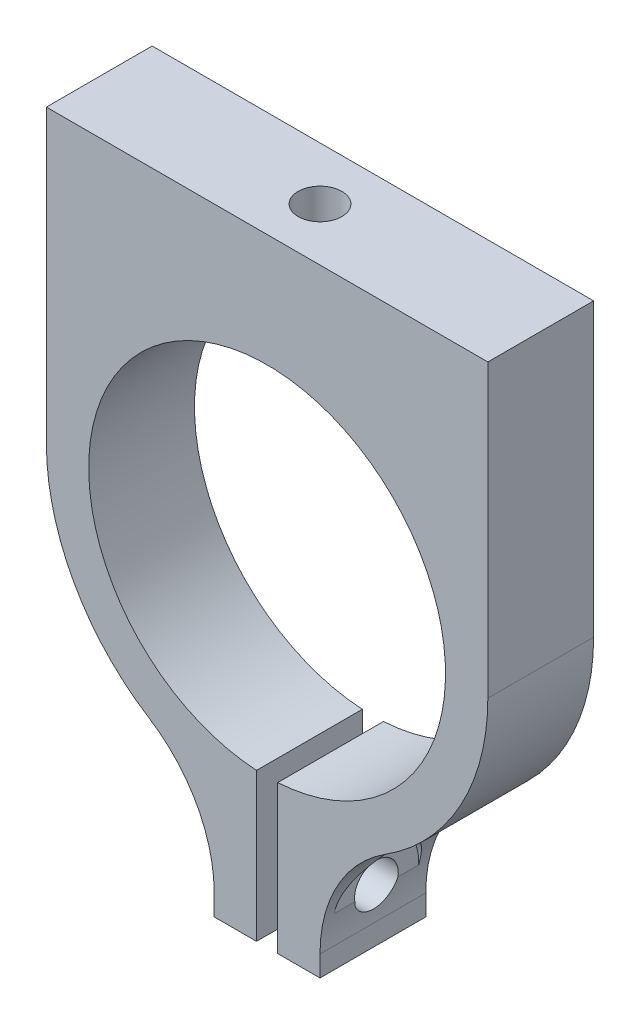
SolidWorks part; units mm, degrees
material "PLA"
ref_plane "Front Plane" through (0, 0, 0) normal (0, 0, 1) x (1, 0, 0)
ref_plane "Top Plane" through (0, 0, 0) normal (0, 1, 0) x (1, 0, 0)
ref_plane "Right Plane" through (0, 0, 0) normal (1, 0, 0) x (0, 0, -1)
sketch "Sketch1" plane through (0, 0, 0) normal (0, 0, 1) x (1, 0, 0)
  line L0 (-15.65, 0) -> (-15.65, 15.65)
  line L1 (-15.65, 15.65) -> (15.65, 15.65)
  line L2 (15.65, 15.65) -> (15.65, 0)
  line L4 (-0.75, -18.6277) -> (0.75, -18.6277)
  line L5 (-0.75, -18.6277) -> (-0.75, -12.6277)
  line L6 (-0.75, -12.6277) -> (0.75, -12.6277)
  line L7 (0.75, -18.6277) -> (0.75, -12.6277)
  line L8 (0, -44.7868) -> (0, 44.7868) construction
  circle A0 centre (0, 0) radius 12.65
  circle A1 centre (0, 0) radius 15.65
  dimension "D1" = 25.3
  dimension "D2" = 31.3
  dimension "D3" = 1.5
  dimension "D4" = 0.75
  dimension "D5" = 6
extrude "Boss-Extrude1" add sketch "Sketch1" along normal mid plane 40 contours A1 L1 L0 | A1 L2 L1 | A1 L5 A0 L7 region at (-12.1543, 12.1543, 0) region at (-10.7533, 10.7533, 0) region at (12.1543, 12.1543, 0)
sketch "Sketch2" plane through (0, 0, 0) normal (0, 0, 1) x (1, 0, 0)
  line L1 (-0.75, -12.6277) -> (-3.75, -12.6277)
  line L2 (-0.75, -12.6277) -> (-0.75, -23.1277)
  line L3 (-0.75, -23.1277) -> (-3.75, -23.1277)
  line L4 (-3.75, -12.6277) -> (-3.75, -23.1277)
  line L5 (0.75, -12.6277) -> (3.75, -12.6277)
  line L6 (0.75, -12.6277) -> (0.75, -23.1277)
  line L7 (0.75, -23.1277) -> (3.75, -23.1277)
  line L8 (3.75, -12.6277) -> (3.75, -23.1277)
  dimension "D1" = 3
  dimension "D2" = 10.5
extrude "Boss-Extrude2" add sketch "Sketch2" along normal mid plane 40
sketch "Sketch4" plane through (0, 15.65, 0) normal (0, 1, 0) x (1, 0, 0)
  line L0 (-15.65, -20) -> (-15.65, 20) construction
  line L1 (-15.65, 20) -> (15.65, 20)
  line L2 (-15.65, 20) -> (-15.65, -20)
  line L3 (-15.65, -20) -> (15.65, -20)
  line L4 (15.65, 20) -> (15.65, -20)
  line L5 (15.65, -20) -> (15.65, 20) construction
  line L6 (-44.2539, 0) -> (44.2539, 0) construction
  line M5 (15.65, 20) -> (-15.65, 20)
  line M6 (-15.65, 20) -> (-15.65, -20)
  line M7 (-15.65, -20) -> (15.65, -20)
  line M8 (15.65, -20) -> (15.65, 20)
  dimension "D1" = 40
  dimension "D2" = 20
extrude "Boss-Extrude3" add sketch "Sketch4" along normal blind 5 contours M8 M5 M6 M7 region at (0, 15.65, 0)
sketch "Sketch5" plane through (15.65, 0, 0) normal (1, 0, 0) x (0, 0, -1)
  line L0 (-20, -23.1277) -> (20, -23.1277) construction
  line L1 (-12.5, 14.65) -> (12.5, 14.65)
  line L2 (-12.5, 14.65) -> (-12.5, -23.1277)
  line L3 (-12.5, -23.1277) -> (12.5, -23.1277)
  line L4 (12.5, 14.65) -> (12.5, -23.1277)
  line L5 (0, 44.2539) -> (0, -44.2539) construction
  line L6 (-20, 20.65) -> (20, 20.65) construction
  dimension "D1" = 25
  dimension "D2" = 12.5
  dimension "D3" = 6
extrude "Cut-Extrude2" cut sketch "Sketch5" along direction (-1, 0, 0) on the side against the normal offset from surface (13.65 mm away) 2 up to plane "Right Plane"
sketch "Sketch6" plane through (0, 20.65, 0) normal (0, 1, 0) x (1, 0, 0)
  line L0 (-44.2539, 0) -> (44.2539, 0) construction
  line L1 (-8.8388, 8.8388) -> (8.8388, 8.8388) construction
  line L2 (-8.8388, 8.8388) -> (-8.8388, -8.8388) construction
  line L3 (-8.8388, -8.8388) -> (8.8388, -8.8388) construction
  line L4 (8.8388, 8.8388) -> (8.8388, -8.8388) construction
  line L5 (0, -44.7868) -> (0, 44.7868) construction
  circle A0 centre (-8.8388, 8.8388) radius 1.55
  circle A1 centre (8.8388, 8.8388) radius 1.55
  circle A2 centre (8.8388, -8.8388) radius 1.55
  circle A3 centre (-8.8388, -8.8388) radius 1.55
  point P6 (-8.8388, 0)
  point P7 (0, 8.8388)
  dimension "D1" = 25
  dimension "D2" = 3.1
extrude "MotorMountHoles" cut sketch "Sketch6" against normal up to surface (6 mm away) up to face at (8.825, 14.65, 0)
sketch "Sketch7" plane through (0, 14.65, 0) normal (0, -1, 0) x (1, 0, 0)
  circle A0 centre (8.8388, 8.8388) radius 2.55
  dimension "D1" = 5.1
extrude "M3ScrewHeadGuide" [suppressed] add sketch "Sketch7" along normal blind 3
sketch "Sketch8" plane through (-3.75, 0, 0) normal (-1, 0, 0) x (0, 0, 1)
  line L1 (20, -15.1941) -> (20, -23.1277) construction
  line L2 (20, -15.1941) -> (-20, -15.1941) construction
  line L3 (-12.5, -23.1277) -> (-12.5, -15.1941) construction
  line L4 (20, -15.1941) -> (-20, -15.1941) construction
  circle A0 centre (16.25, -19.1941) radius 1.55
  circle A1 centre (-16.25, -19.1941) radius 1.55
  dimension "D1" = 3.1
  dimension "D2" = 3.75
  dimension "D3" = 4
  dimension "D4" = 3.75
  dimension "D5" = 4
extrude "ClampHoles" cut sketch "Sketch8" against normal up to surface (7.5 mm away) up to face at (3.75, -19.1609, 16.25)
sketch "Sketch9" plane through (0, 0, 20) normal (0, 0, 1) x (1, 0, 0)
  line L1 (-0.75, -12.6277) -> (0.75, -12.6277)
  line L2 (-0.75, -12.6277) -> (-0.75, -7.9648)
  line L3 (-0.75, -7.9648) -> (0.75, -7.9648)
  line L4 (0.75, -12.6277) -> (0.75, -7.9648)
  circle A0 centre (0, 0) radius 12.65
  circle A1 centre (0, 0) radius 8
  arc M13 (-0.75, -12.6277) -> (0.75, -12.6277) centre (0, 0) cw
  dimension "D1" = 16
  dimension "D2" = 25.3
extrude "EndStopper" add sketch "Sketch9" against normal blind 2 contours A1 L4 L2 M13 region at (-8.4304, 8.946, 20)
sketch "Sketch10" plane through (0, 0, 0) normal (1, 0, 0) x (0, 0, -1)
  line L1 (-12.5, 14.65) -> (12.5, 14.65)
  line L2 (-12.5, 14.65) -> (-12.5, -23.1277)
  line L3 (-12.5, -23.1277) -> (12.5, -23.1277)
  line L4 (12.5, 14.65) -> (12.5, -23.1277)
extrude "Cut-Extrude7" cut sketch "Sketch10" along normal offset from surface (13.65 mm away) 2 from surface up to plane "Right Plane" starting at face at (-15.65, 10.325, 0)
sketch "Sketch11" plane through (-2, 0, 0) normal (-1, 0, 0) x (0, 0, 1)
  line L1 (-12.5, -12.4909) -> (12.5, -12.4909)
  line L2 (-12.5, -12.4909) -> (-12.5, -23.1277)
  line L3 (-12.5, -23.1277) -> (12.5, -23.1277)
  line L4 (12.5, -12.4909) -> (12.5, -23.1277)
extrude "Cut-Extrude8" cut sketch "Sketch11" against normal up to surface (4 mm away) up to face at (2, -17.8093, 0)
fillet "Fillet1" radius 10 4 edges at (-3.75, -15.1941, -16.25) (3.75, -15.1941, 16.25) (3.75, -15.1941, -16.25) (-3.75, -15.1941, 16.25)
sketch "Sketch12" plane through (0, 0, 0) normal (1, 0, 0) x (0, 0, -1)
  line L0 (-30.459, 12.329) -> (0, 36.5616) construction
  line L1 (0, 44.2539) -> (0, -44.2539) construction
  line L2 (-10.1062, 43.5673) -> (4.6194, 25.058) construction
  line L3 (0, 36.5616) -> (-30.459, 12.329)
ref_plane "Plane1" through (0, 11.9634, -15.0373) normal (0, 0.6226, -0.7826) x (-1, 0, 0)
sketch "Sketch13" plane through (0, 11.9634, -15.0373) normal (0, 0.6226, -0.7826) x (-1, 0, 0)
  line L0 (0, 44.7868) -> (0, -44.7868) construction
  line L1 (-5, 34.4844) -> (5, 34.4844)
  line L2 (-5, 34.4844) -> (-5, 24.4844)
  line L3 (-5, 24.4844) -> (5, 24.4844)
  line L4 (5, 34.4844) -> (5, 24.4844)
  dimension "D1" = 10
  dimension "D2" = 10
  dimension "D3" = 5
sweep "Cut-Sweep1" cut profiles "Sketch13" path "Sketch12"
sketch "Sketch15" plane through (0, 0, 0) normal (1, 0, 0) x (0, 0, -1)
  circle A0 centre (16.25, -19.1941) radius 3
  dimension "D1" = 6
extrude "Cut-Extrude10" cut sketch "Sketch15" along normal up to surface (0.0571 mm away) from offset 4 contours A0 up to face at (5.528, -17.1346, -16.25)
sketch "Sketch16" plane through (0, 0, 0) normal (1, 0, 0) x (0, 0, -1)
  line L0 (12.5, -23.1277) -> (20, -23.1277) construction
  line L1 (12.9591, -19.1941) -> (14.6046, -22.0441)
  line L2 (14.6046, -22.0441) -> (17.8954, -22.0441)
  line L3 (17.8954, -22.0441) -> (19.5409, -19.1941)
  line L4 (19.5409, -19.1941) -> (17.8954, -16.3441)
  line L5 (17.8954, -16.3441) -> (14.6046, -16.3441)
  line L6 (14.6046, -16.3441) -> (12.9591, -19.1941)
  circle A0 centre (16.25, -19.1941) radius 2.85 construction
  dimension "D1" = 5.7
extrude "Cut-Extrude11" cut sketch "Sketch16" against normal blind 3 from offset 4 offset against normal yes
mirror "Mirror1" about plane through (0, 0, 0) normal (0, 0, 1) of "Cut-Extrude10", "Cut-Extrude11"
sketch "Sketch17" plane through (0, 20.65, 0) normal (0, 1, 0) x (1, 0, 0)
  circle A0 centre (0, 0) radius 6
  dimension "D1" = 12
extrude "Shaft Clearance" cut sketch "Sketch17" against normal blind 0.4
sketch "Sketch18" plane through (0, 0, 0) normal (1, 0, 0) x (0, 0, -1)
  line L1 (12.5, -28.6239) -> (-47.9707, -28.6239)
  line L2 (12.5, -28.6239) -> (12.5, 38.7327)
  line L3 (12.5, 38.7327) -> (-47.9707, 38.7327)
  line L4 (-47.9707, -28.6239) -> (-47.9707, 38.7327)
extrude "Cut-Extrude12" cut sketch "Sketch18" against normal mid plane 50
sketch "Sketch19" plane through (0, 20.65, 0) normal (0, 1, 0) x (1, 0, 0)
  line L0 (0, -44.7868) -> (0, 44.7868) construction
  line L1 (15.65, 20) -> (-15.65, 20) construction
  circle A0 centre (0, 16.25) radius 1.55
  dimension "D1" = 3.1
  dimension "D2" = 3.75
extrude "Cut-Extrude13" cut sketch "Sketch19" against normal blind 7
sketch "Sketch20" plane through (0, 20.65, 0) normal (0, 1, 0) x (1, 0, 0)
  line L0 (15.65, 12.5) -> (-15.65, 12.5) construction
  line L4 (-3.2909, 16.25) -> (-1.6454, 13.4)
  line L5 (-1.6454, 13.4) -> (1.6454, 13.4)
  line L6 (1.6454, 13.4) -> (3.2909, 16.25)
  line L7 (-1.6454, 19.1) -> (-3.2909, 16.25) [skipped]
  line L8 (3.2909, 16.25) -> (1.6454, 19.1) [skipped]
  line L9 (-3.2909, 16.25) -> (-3.2909, 19.1)
  line L10 (3.2909, 16.25) -> (3.2909, 19.1)
  line L11 (1.6454, 19.1) -> (-1.6454, 19.1) [skipped]
  line L12 (3.2909, 19.1) -> (-3.2909, 19.1)
  circle A0 centre (0, 16.25) radius 2.85 construction
  dimension "D1" = 5.7
extrude "Cut-Extrude14" cut sketch "Sketch20" against normal blind 2.6 from offset 3 offset against normal yes
sketch "Sketch21" plane through (0, 20.65, 0) normal (0, 1, 0) x (1, 0, 0)
  line L0 (15.65, 12.5) -> (-15.65, 12.5) construction
  line L1 (-8.6, 18.75) -> (-3.6, 18.75)
  line L2 (-8.6, 18.75) -> (-8.6, 13.75)
  line L3 (-8.6, 13.75) -> (-3.6, 13.75)
  line L4 (-3.6, 18.75) -> (-3.6, 13.75)
  line L5 (3.6, 18.75) -> (8.6, 18.75)
  line L6 (3.6, 18.75) -> (3.6, 13.75)
  line L7 (3.6, 13.75) -> (8.6, 13.75)
  line L8 (8.6, 18.75) -> (8.6, 13.75)
  line L9 (0, -44.7868) -> (0, 44.7868) construction
  dimension "D1" = 5
  dimension "D2" = 1.25
  dimension "D3" = 7.2
  dimension "D4" = 3.6
extrude "Boss-Extrude4" [suppressed] add sketch "Sketch21" along normal blind 1.7
equation "\"InnerDiam\"=25.3"
equation "\"D1@Sketch1\"=\"InnerDiam\""
equation "\"OuterDiam\"=31.3"
equation "\"D2@Sketch1\"=\"OuterDiam\""
equation "\"TightenGap\"=1.5"
equation "\"D3@Sketch1\"=\"TightenGap\""
equation "\"D4@Sketch1\"=\"TightenGap\"/2"
equation "\"D5@Sketch1\"=\"OuterDiam\"-\"InnerDiam\""
equation "\"ClampLen\"=10.5"
equation "\"D2@Sketch2\"=\"ClampLen\""
equation "\"Thick\"=40"
equation "\"D1@Boss-Extrude2\"=\"Thick\""
equation "\"D1@Boss-Extrude1\"=\"Thick\""
equation "\"MotBaseThick\"=5"
equation "\"D1@Boss-Extrude3\"=\"MotBaseThick\""
equation "\"TopPlateLen\"=35"
equation "\"D1@Sketch4\"=\"Thick\""
equation "\"D2@Sketch4\"=\"Thick\"/2"
equation "\"D1@Sketch5\"=\"Thick\"- 2 * \"ClampWidth\""
equation "\"D2@Sketch5\"=(\"Thick\"- 2 * \"ClampWidth\")/2"
equation "\"MotorMountDiam\"=25"
equation "\"D1@Sketch6\"=\"MotorMountDiam\""
equation "\"ClampWidth\"= 7.5"
equation "\"D2@Sketch8\"=\"ClampWidth\"/2"
equation "\"D3@Sketch8\"=(\"ClampLen\"- 2.5)/2"
equation "\"D4@Sketch8\"=\"ClampWidth\"/2"
equation "\"D5@Sketch8\"=(\"ClampLen\"- 2.5)/2"
equation "\"D2@Sketch9\"=\"InnerDiam\""
equation "\"D19@Cut-Extrude2\"=\"OuterDiam\"/2"
